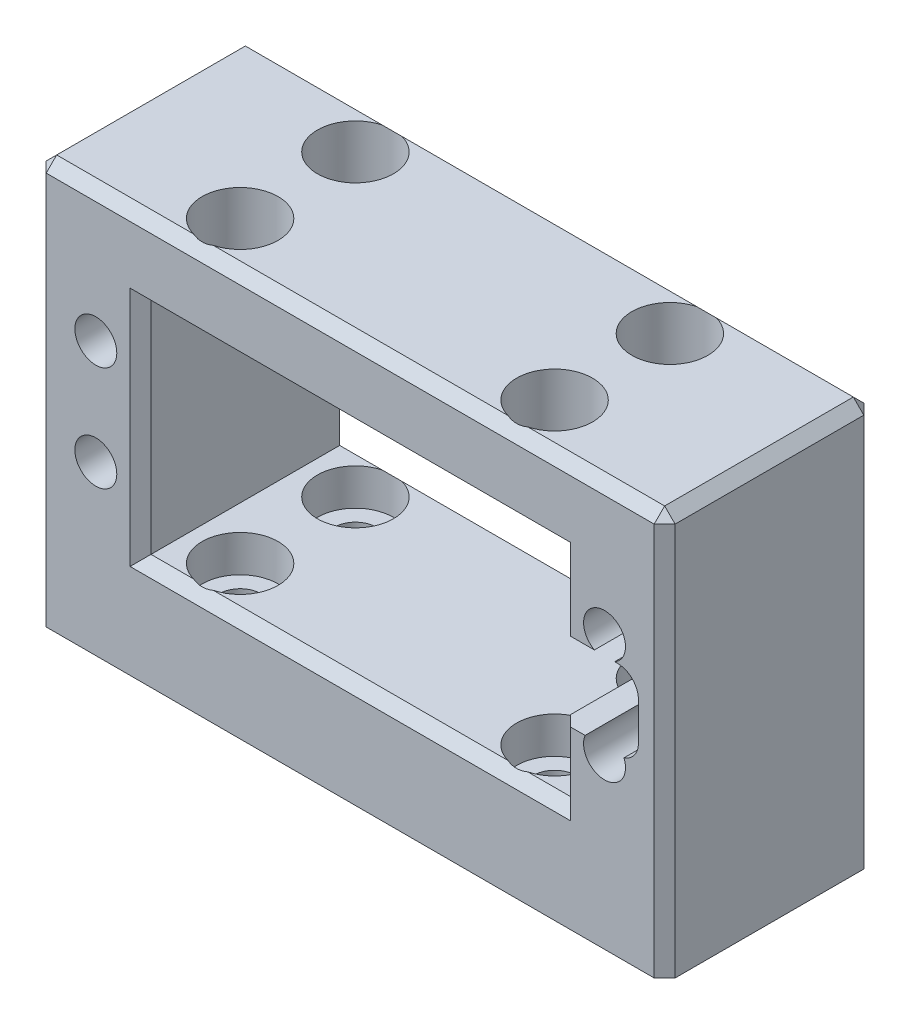
SolidWorks part; units mm, degrees
ref_plane "Front" through (0, 0, 0) normal (0, 0, 1) x (1, 0, 0)
ref_plane "Top" through (0, 0, 0) normal (0, 1, 0) x (1, 0, 0)
ref_plane "Right" through (0, 0, 0) normal (1, 0, 0) x (0, 0, -1)
sketch "Sketch1" plane through (0, 0, 0) normal (0, 0, 1) x (1, 0, 0)
  line L0 (-30, 0) -> (-30, 28.5)
  line L1 (55, 0) -> (-55, 0) construction
  line L4 (-30, 28.5) -> (30, 28.5)
  line L6 (0, -55) -> (0, 55) construction
  line L7 (20, 21) -> (-20, 21)
  line L8 (-20, 21) -> (-20, 0)
  line L9 (-20, 0) -> (-30, 0)
  line L10 (20, 0) -> (30, 0)
  line L11 (20, 21) -> (20, 0)
  line L14 (30, 0) -> (30, 28.5)
  line L17 (-30, 0) -> (-30, 2)
  line L22 (30, 0) -> (30, 2)
  line L23 (-30, 0) -> (-30, -10)
  line L24 (-30, 0) -> (30, 0)
  line L26 (-30, -10) -> (30, -10)
  line L28 (20, 14.25) -> (27.5, 14.25)
  line L29 (20, 14.25) -> (20, 6.75)
  line L30 (20, 6.75) -> (27.5, 6.75)
  line L31 (27.5, 14.25) -> (27.5, 6.75)
  line L32 (30, 0) -> (30, -10)
  circle A0 centre (-24.265, 16) radius 2
  circle A1 centre (-24.265, 6) radius 2
  circle A2 centre (24.265, 6) radius 2
  circle A3 centre (24.265, 16) radius 2
  point P16 (0, 21)
  point P17 (0, 28.5)
  point P35 (27.5, 10.5)
  point P36 (20, 10.5)
  dimension "D5" = 4
  dimension "D6" = 7.5
  dimension "D1" = 7.5
  dimension "D2" = 48.53
  dimension "D3" = 10
  dimension "D4" = 20
  dimension "D7" = 10
  dimension "D8" = 21
  dimension "D11" = 5
  dimension "D12" = 6
  dimension "D13" = 7.5
extrude "Boss-Extrude1" add sketch "Sketch1" along normal blind 20 contours L0 | L10 L14 L4 L0 L9 L8 L7 L11 A2 A1 A0 A3 | L14 | L10 L24 L9 L26 | L24 L23 L26 L32 region at (-29.3358, 1, 0) region at (0, -5, 0)
sketch "Sketch3" plane through (0, 0, 0) normal (0, 1, 0) x (1, 0, 0)
  line L0 (-15, -4.5) -> (-15, -15.5) construction
  line L2 (0, -11) -> (0, 11) construction
  line L3 (-30, -20) -> (-30, 0) construction
  circle A0 centre (-15, -4.5) radius 2
  circle A1 centre (-15, -15.5) radius 2
  circle A2 centre (15, -15.5) radius 2
  circle A3 centre (15, -4.5) radius 2
  point P6 (-30, -10)
  point P7 (-15, -10)
  point P14 (0, 0)
  point P15 (0, 0)
  dimension "D1" = 4
  dimension "D2" = 11
  dimension "D3" = 15
extrude "Cut-Extrude2" cut sketch "Sketch3" against normal through all both and the other way through all
sketch "Sketch4" plane through (0, 0, 0) normal (0, 1, 0) x (1, 0, 0)
  circle A0 centre (-15, -4.5) radius 2 construction
  circle A1 centre (-15, -4.5) radius 2
  circle A2 centre (-15, -15.5) radius 2 construction
  circle A3 centre (-15, -15.5) radius 2
  circle A4 centre (15, -4.5) radius 2 construction
  circle A5 centre (15, -15.5) radius 2 construction
  circle A6 centre (15, -4.5) radius 2
  circle A7 centre (15, -15.5) radius 2
  circle A8 centre (-15, -4.5) radius 3.625
  circle A9 centre (-15, -15.5) radius 3.625
  circle A10 centre (15, -15.5) radius 3.625
  circle A11 centre (15, -4.5) radius 3.625
  dimension "D1" = 7.25
extrude "Cut-Extrude4" cut sketch "Sketch4" against normal blind 3.5 and the other way through all
fillet "Fillet1" radius 2 2 edges at (27.5, 6.75, 10) (27.5, 14.25, 10)
chamfer "Chamfer1" distance 1 angle 45 18 edges at (20, 17.625, 20) (20, 3.375, 20) (0, 0, 20) (-20, 10.5, 20) (0, 21, 20) (30, 28.5, 10) (30, 9.25, 20) (0, 28.5, 20) (30, 9.25, 0) (0, 28.5, 0) (-30, 9.25, 0) (-30, 28.5, 10) (-30, 9.25, 20) (20, 3.375, 0) (0, 0, 0) (-20, 10.5, 0) (20, 17.625, 0) (0, 21, 0)
